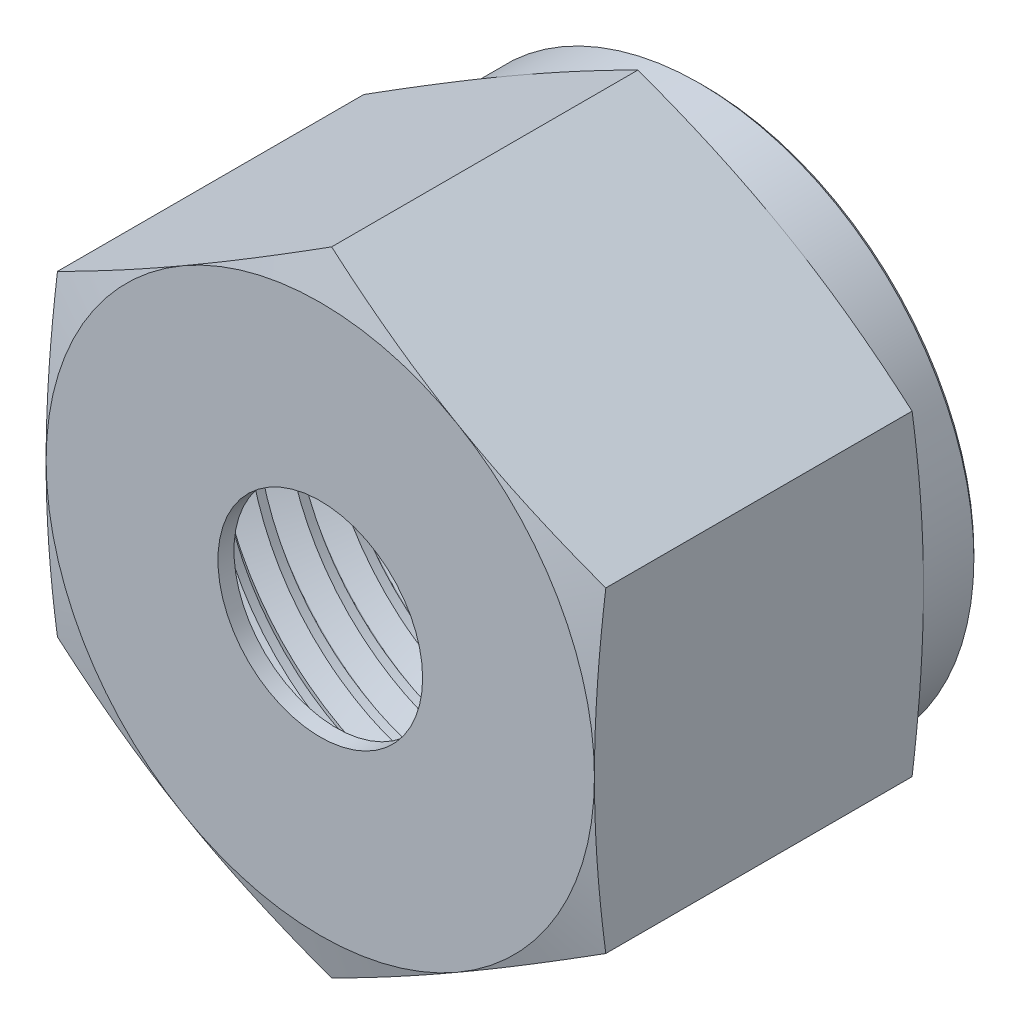
SolidWorks part; units mm, degrees
material "AISI 316 Stainless Steel Sheet (SS)"
ref_plane "Front Plane" through (0, 0, 0) normal (0, 0, 1) x (1, 0, 0)
ref_plane "Top Plane" through (0, 0, 0) normal (0, 1, 0) x (1, 0, 0)
ref_plane "Right Plane" through (0, 0, 0) normal (1, 0, 0) x (0, 0, -1)
sketch "Sketch0" plane through (0, 0, 0) normal (1, 0, 0) x (0, 0, -1)
  line L0 (0, 0) -> (-25.9334, 0) construction
  line L4 (-25.9334, 15.875) -> (-25.9334, -15.875) construction
  line L5 (-25.9334, 15.875) -> (-25.9334, -15.875) construction
  line L6 (-25.9334, 10.5918) -> (-25.9334, -10.5918) construction
  line L7 (0, 13.4937) -> (0, -13.4937) construction
  line L8 (0, -13.4874) -> (0, 13.4874) construction
  line L9 (0, -13.4874) -> (-2.1167, -13.4874) construction
  point P16 (-22.0472, 0)
  point P20 (-19.1262, 0)
  point P22 (-13.6398, 0)
  point P34 (-3.175, 0)
  point P35 (-22.225, 0)
  dimension "P" = 31.75
  dimension "M" = 25.9334
  dimension "L" = 22.0472
  dimension "S" = 19.1262
  dimension "Q" = 13.6398
  dimension "A" = 21.1836
  dimension "C" = 31.75
  dimension "T" = 26.9875
  dimension "B" = 3.175
  dimension "J" = 19.05
  dimension "H" = 26.9748
  dimension "Pitch" = 2.1167
sketch "Sketch1" plane through (0, 0, 0) normal (0, 0, 1) x (1, 0, 0)
  line L1 (0, 18.3309) -> (-15.875, 9.1654)
  line L2 (-15.875, 9.1654) -> (-15.875, -9.1654)
  line L3 (-15.875, -9.1654) -> (0, -18.3309)
  line L4 (0, -18.3309) -> (15.875, -9.1654)
  line L5 (15.875, -9.1654) -> (15.875, 9.1654)
  line L6 (15.875, 9.1654) -> (0, 18.3309)
  circle A0 centre (0, 0) radius 15.875 construction
extrude "Boss-Extrude1" add sketch "Sketch1" along normal up to vertex (25.9334 mm away) up to point (0, 0, 25.9334)
sketch "Sketch2" plane through (0, 0, 0) normal (1, 0, 0) x (0, 0, -1)
  line L0 (-25.9334, 20.7867) -> (-25.9334, 15.875)
  line L1 (-25.9334, 15.875) -> (-22.225, 15.875)
  line L2 (-22.225, 15.875) -> (-21.567, 18.3309)
  line L3 (-25.9334, 18.3309) -> (0, 18.3309) construction
  line L4 (-21.567, 18.3309) -> (-3.833, 18.3309)
  line L5 (-3.833, 18.3309) -> (-3.175, 15.875)
  line L6 (-3.175, 15.875) -> (-22.225, 15.875) construction
  line L7 (-3.175, 15.875) -> (0, 15.875)
  line L8 (0, 15.875) -> (0, 20.7867)
  line L9 (-25.9334, 20.7867) -> (0, 20.7867)
  line L10 (-3.175, 15.875) -> (-3.175, 0) construction
  line L11 (-22.225, 15.875) -> (-22.225, 0) construction
  line L12 (-25.9334, 10.5918) -> (-25.9334, 0)
  line L13 (-25.9334, 15.875) -> (-25.9334, -15.875) construction
  line L14 (-25.9334, 0) -> (0, 0)
  line L15 (0, 0) -> (0, 12.7204)
  line L16 (-22.0472, 10.5918) -> (-22.0472, 0) construction
  line L17 (-22.0472, 10.5918) -> (-22.0472, 12.4664)
  line L18 (-21.7932, 12.7204) -> (0, 12.7204)
  line L19 (-22.0472, 10.5918) -> (-25.9334, 10.5918)
  line L23 (-19.1262, 0) -> (-19.1262, 12.7204) construction
  arc A0 (-22.0472, 12.4664) -> (-21.7932, 12.7204) centre (-21.7932, 12.4664) cw
  dimension "D3" = 0.254
  dimension "D1" = 15
  dimension "D2" = 15
  dimension "D4" = 0.7733
revolve "Cut-Revolve1" cut sketch "Sketch2" angle 360 about L0 other way angle 360
sketch "Sketch3" plane through (0, 0, 0) normal (0, 0, -1) x (-1, 0, 0)
  circle A0 centre (0, 0) radius 12.7204
  circle A1 centre (0, 0) radius 12.7204 construction
  point P3 (0, 12.7204)
fillet "Fillet1" radius 1.5748 1 edges at (15.875, 0, 25.9334)
chamfer "Chamfer1" distance 0.254 angle 45 1 edges at (15.875, 0, 0)
chamfer "Chamfer2" distance 0.254 angle 45 2 edges at (0, 10.5918, 22.0472) (0, 10.5918, 25.9334)
ref_axis "Centre Axis 1" through (0, 0, 25.2505) along (0, 0, -1)
curve "Helix/Spiral1" pitch 2.1167 height 21.2429 radius 12.7204 centre (0, 0, 0) axis (0, 0, 1) start towards (0, 1, 0) parameters "Pitch"=2.1167
sketch "Sketch4" plane through (0, 0, 0) normal (1, 0, 0) x (0, 0, -1)
  line L0 (-0.248, 12.2908) -> (1.8686, 12.2908) construction
  line L1 (1.8686, 12.2908) -> (0.8103, 14.1239) construction
  line L2 (0.8103, 14.1239) -> (-0.248, 12.2908) construction
  line L3 (0.7111, 13.952) -> (0.9095, 13.952) construction
  line L4 (0.8103, 12.7204) -> (0.8103, 12.2908) construction
  line L5 (0, 12.7204) -> (1.6206, 12.7204) construction
  line L6 (0.8103, 14.1239) -> (0.8103, 13.952) construction
  line L7 (0.7111, 13.952) -> (-0.124, 12.5056)
  line L8 (-0.124, 12.5056) -> (1.7446, 12.5056)
  line L9 (1.7446, 12.5056) -> (0.9095, 13.952)
  arc A0 (0.9095, 13.952) -> (0.7111, 13.952) centre (0.8103, 13.8947) ccw
  point P6 (0.8103, 12.5056)
  dimension "D1" = 2.1167
  dimension "D2" = 1.8331
  dimension "D4" = 0.4296
  dimension "D3" = 0.1719
  dimension "D5" = 1.2316
sweep "Cut-Sweep1" cut profiles "Sketch4" path "Helix/Spiral1" align with end faces yes
sketch "Sketch5" plane through (0, 0, 0) normal (0, 0, -1) x (-1, 0, 0)
  circle A0 centre (0, 0) radius 13.4874
extrude "Cut-Extrude1" cut sketch "Sketch5" against normal through all draft 45
sketch "Sketch6" plane through (0, 0, 0) normal (1, 0, 0) x (0, 0, -1)
  line L0 (-22.0472, 14.1239) -> (-13.6398, 14.1239)
  line L1 (-13.6398, 14.1239) -> (-19.1262, 12.7204)
  line L2 (-19.1262, 12.7204) -> (-22.0472, 12.7204)
  line L3 (-22.0472, 12.7204) -> (-22.0472, 14.1239)
  line L4 (-13.6398, 0) -> (-13.6398, 14.1239) construction
  line L5 (-19.1262, 0) -> (-19.1262, 12.7204) construction
  line L7 (-22.0472, 12.7204) -> (-22.0472, 0) construction
  line L8 (-21.7932, 12.7204) -> (0, 12.7204) construction
  line L9 (-13.6398, 14.1239) -> (0.8103, 14.1239) construction
revolve "Revolve1" add sketch "Sketch6" angle 360 about L0
sketch "SketchX" plane through (0, 0, 0) normal (0, 0, -1) x (-1, 0, 0)
  line L0 (0, 0) -> (-6.7437, 11.6804) construction
  line L1 (-7.9375, 13.7482) -> (-15.875, 9.1654) construction
  circle A0 centre (0, 0) radius 13.4874 construction
sketch "Sketch7" plane through (0, 0, 0) normal (1, 0, 0) x (0, 0, -1)
  line L0 (-22.225, 15.875) -> (-22.225, -18.6682) construction
  line L2 (-22.225, -18.6682) -> (-31.8363, -18.6682)
  line L3 (-22.225, -18.6682) -> (-22.225, 18.6682)
  line L4 (-22.225, 18.6682) -> (-31.8363, 18.6682)
  line L5 (-31.8363, -18.6682) -> (-31.8363, 18.6682)
extrude "Cut-Extrude2" cut sketch "Sketch7" against normal mid plane 38.1
sketch "Sketch8" plane through (0, 0, 0) normal (1, 0, 0) x (0, 0, -1)
  line L0 (-22.225, 13.5464) -> (-22.225, -13.55) construction
  line L1 (0, 0) -> (2.6361, 0) construction
  line L2 (-21.2965, 5.9264) -> (-22.225, 5.9264)
  line L3 (-21.2965, 5.9264) -> (-21.2965, 13.5464)
  line L4 (-21.2965, 13.5464) -> (-22.225, 13.5464)
  line L5 (-22.225, 5.9264) -> (-22.225, 13.5464)
  line L6 (-22.225, 13.7482) -> (-22.225, 0) construction
  dimension "D1" = 7.62
revolve "Revolve2" add sketch "Sketch8" angle 360 about L1
equation "\"D3@Helix/Spiral1\"= \"Pitch@Sketch0\" + \"S@Sketch0\""
equation "\"D1@Sketch4\"=\"Pitch@Sketch0\""
equation "\"Pitch@Helix/Spiral1\"=\"Pitch@Sketch0\""
